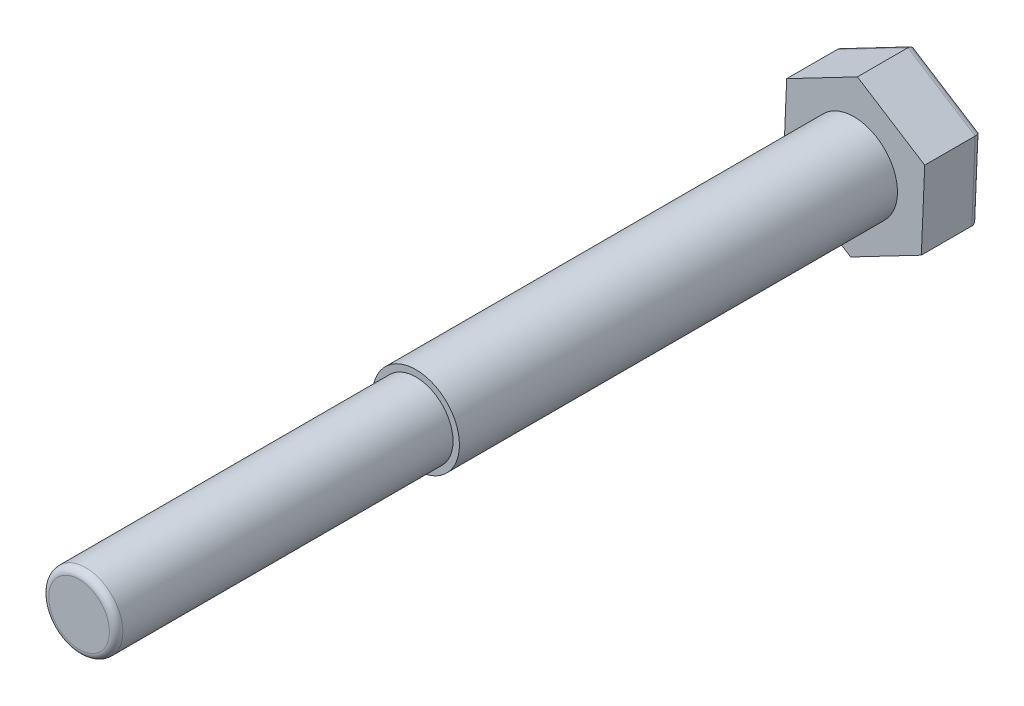
SolidWorks part; units mm, degrees
ref_plane "前视" through (0, 0, 0) normal (0, 0, 1) x (1, 0, 0)
ref_plane "上视" through (0, 0, 0) normal (0, 1, 0) x (1, 0, 0)
ref_plane "右视" through (0, 0, 0) normal (1, 0, 0) x (0, 0, -1)
sketch "草图1" plane through (0, 0, 0) normal (0, 0, 1) x (1, 0, 0)
  line L1 (20.9842, 10.9543) -> (1.0054, 23.65)
  line L2 (1.0054, 23.65) -> (-19.9788, 12.6957)
  line L3 (-19.9788, 12.6957) -> (-20.9842, -10.9543)
  line L4 (-20.9842, -10.9543) -> (-1.0054, -23.65)
  line L5 (-1.0054, -23.65) -> (19.9788, -12.6957)
  line L6 (19.9788, -12.6957) -> (20.9842, 10.9543)
  circle A0 centre (0, 0) radius 20.5 construction
  dimension "D1" = 47.3
  dimension "D2" = 41
extrude "基体-拉伸" add sketch "草图1" along normal blind 17
sketch "草图2" plane through (0, 0, 17) normal (0, 0, 1) x (1, 0, 0)
  circle A0 centre (0, 0) radius 12.9
  dimension "D1" = 25.8
extrude "凸台-拉伸1" add sketch "草图2" along normal blind 130
fillet "圆角3" radius 2 6 edges at (10.9948, 17.3021, 0) (-9.4867, 18.1729, 0) (-20.4815, 0.8707, 0) (-10.9948, -17.3021, 0) (9.4867, -18.1729, 0) (20.4815, -0.8707, 0)
sketch "草图3" plane through (0, 0, 147) normal (0, 0, 1) x (1, 0, 0)
  circle A0 centre (0, 0) radius 11
  dimension "D1" = 22
extrude "凸台-拉伸2" add sketch "草图3" along normal blind 100
fillet "圆角4" radius 2 1 edges at (11, 0, 247)
